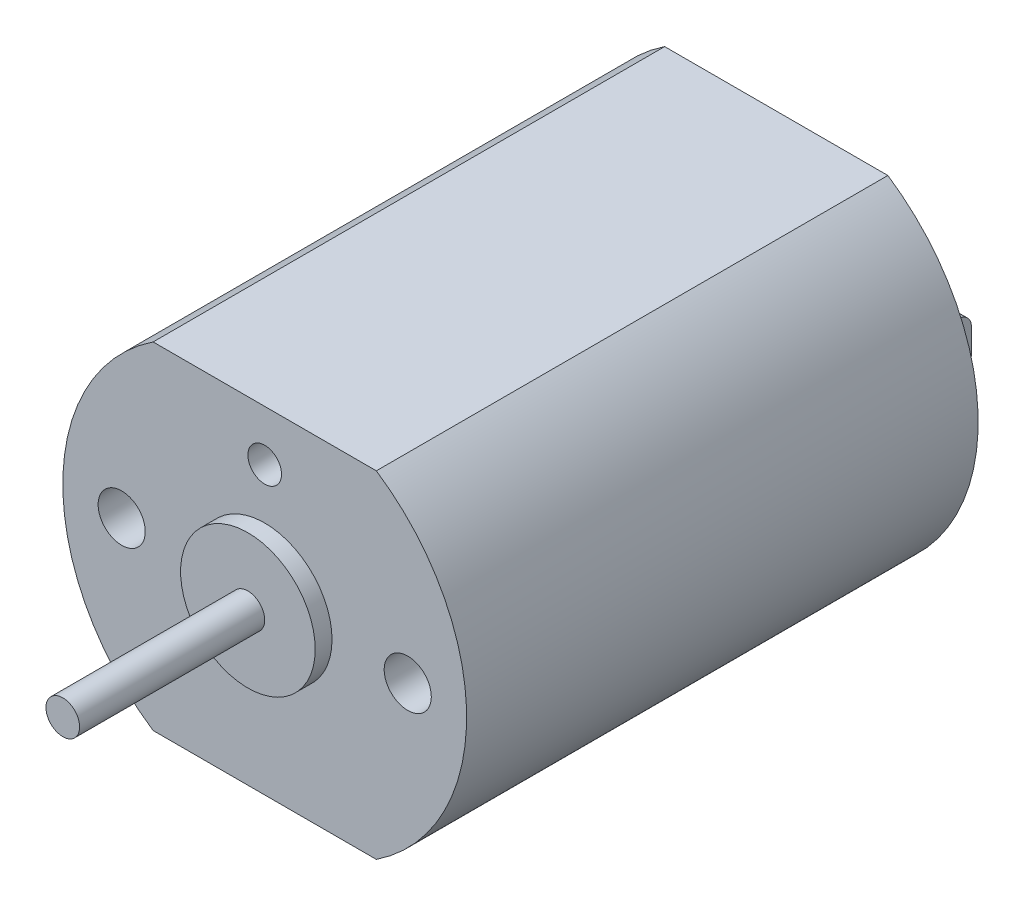
SolidWorks part; units mm, degrees
ref_plane "前视基准面" through (0, 0, 0) normal (0, 0, 1) x (1, 0, 0)
ref_plane "上视基准面" through (0, 0, 0) normal (0, 1, 0) x (1, 0, 0)
ref_plane "右视基准面" through (0, 0, 0) normal (1, 0, 0) x (0, 0, -1)
other "Configuration Table"
sketch "草图1" plane through (0, 0, 0) normal (0, 0, 1) x (1, 0, 0)
  line L0 (3.5, -0.75) -> (3.8, -0.75)
  line L1 (-6, -5) -> (6, -5)
  line L2 (-6, -5) -> (-6, 5)
  line L3 (-6, 5) -> (6, 5)
  line L4 (6, -5) -> (6, 5)
  line L5 (-6, -5) -> (6, 5) construction
  line L6 (-6, 5) -> (6, -5) construction
  line L7 (-3.8, -0.75) -> (-3.5, -0.75)
  line L8 (-3.8, -0.75) -> (-3.8, 0.75)
  line L9 (-3.8, 0.75) -> (-3.5, 0.75)
  line L10 (-3.5, -0.75) -> (-3.5, 0.75)
  line L11 (-3.8, -0.75) -> (-3.5, 0.75) construction
  line L12 (-3.8, 0.75) -> (-3.5, -0.75) construction
  line L13 (3.5, -0.75) -> (3.5, 0.75)
  line L14 (3.5, 0.75) -> (3.8, 0.75)
  line L15 (3.8, -0.75) -> (3.8, 0.75)
  line L16 (-3.5, 0) -> (3.5, 0) construction
  circle A0 centre (0, 0) radius 6
  circle A1 centre (0, 0) radius 2.5
  circle A2 centre (0, 0) radius 1.5
  point P0 (0, 0)
  point P8 (-3.65, 0)
  dimension "D6" = 5
  dimension "D7" = 3
  dimension "D1" = 12
  dimension "D2" = 10
  dimension "D3" = 0.3
  dimension "D4" = 1.5
  dimension "D5" = 7
extrude "凸台-拉伸1" add sketch "草图1" along normal blind 15.2 contours L3 A0 L1 A1 L15 L0 L13 L14 L10 L7 L8 L9 | A1 A2 | A2 | L0 L15 L14 L13 | L7 L10 L9 L8 region at (3.65, 0, 0) region at (-5.1491, -2.7634, 0) region at (-3.65, 0, 0) region at (-2.4293, 0, 0) region at (0, 0, 0)
extrude "凸台-拉伸2" add sketch "草图1<4>" against normal blind 2 contours L13 L14 L15 L0 | L8 L9 L10 L7
sketch "草图1<4>" plane through (0, 0, 0) normal (0, 0, 1) x (1, 0, 0) same geometry as "草图1"
sketch "草图2" plane through (3.8, 0, 0) normal (1, 0, 0) x (0, 0, -1)
  line L0 (0.95, 0) -> (1.05, 0) construction
  line L1 (0.95, 0.45) -> (1.05, 0.45)
  line L2 (0.95, -0.45) -> (1.05, -0.45)
  line L4 (1, 0.75) -> (1, -0.75) construction
  line L5 (2, 0.75) -> (0, 0.75) construction
  line L6 (2, -0.75) -> (0, -0.75) construction
  arc A0 (0.95, 0.45) -> (0.95, -0.45) centre (0.95, 0) ccw
  arc A1 (1.05, -0.45) -> (1.05, 0.45) centre (1.05, 0) ccw
  point P3 (1, 0)
  dimension "D2" = 0.45
  dimension "D1" = 0.1
extrude "切除-拉伸2" cut sketch "草图2" against normal through all
fillet "圆角1" radius 0.4 4 edges at (-3.65, 0.75, -2) (-3.65, -0.75, -2) (3.65, 0.75, -2) (3.65, -0.75, -2)
extrude "凸台-拉伸3" add sketch "草图1<5>" against normal blind 1.2 contours A1 A2 | A2 region at (-2.4293, 0, 0) region at (0, 0, 0)
sketch "草图1<5>" plane through (0, 0, 0) normal (0, 0, 1) x (1, 0, 0) same geometry as "草图1"
extrude "切除-拉伸1" cut sketch "草图1<7>" along normal blind 0.6 from surface contours A2 region at (0, 0, 0) starting at face at (2.5, 0, -1.2)
sketch "草图1<7>" plane through (0, 0, 0) normal (0, 0, 1) x (1, 0, 0) same geometry as "草图1"
fillet "圆角2" radius 0.4 1 edges at (2.5, 0, -1.2)
sketch "草图3" plane through (0, 0, 15.2) normal (0, 0, 1) x (1, 0, 0)
  circle A0 centre (0, 0) radius 2
  circle A1 centre (0, 0) radius 0.5
  dimension "D1" = 4
  dimension "D2" = 1
extrude "凸台-拉伸4" add sketch "草图3" along normal blind 0.5 contours A0
extrude "凸台-拉伸5" add sketch "草图3<3>" along normal blind 6 contours A1 region at (0, 0, 15.2)
sketch "草图3<3>" plane through (0, 0, 15.2) normal (0, 0, 1) x (1, 0, 0) same geometry as "草图3"
sketch "草图4" plane through (0, 0, 15.2) normal (0, 0, 1) x (1, 0, 0)
  line L0 (-4.25, 0) -> (4.25, 0) construction
  line L1 (0, 0) -> (0, 5) construction
  line L2 (-3.3166, 5) -> (3.3166, 5) construction
  circle A0 centre (-4.25, 0) radius 0.7
  circle A1 centre (4.25, 0) radius 0.7
  circle A2 centre (0, 3.5) radius 0.5
  dimension "D1" = 1.4
  dimension "D2" = 8.5
  dimension "D3" = 1
  dimension "D4" = 3.5
extrude "切除-拉伸3" cut sketch "草图4" against normal blind 1
